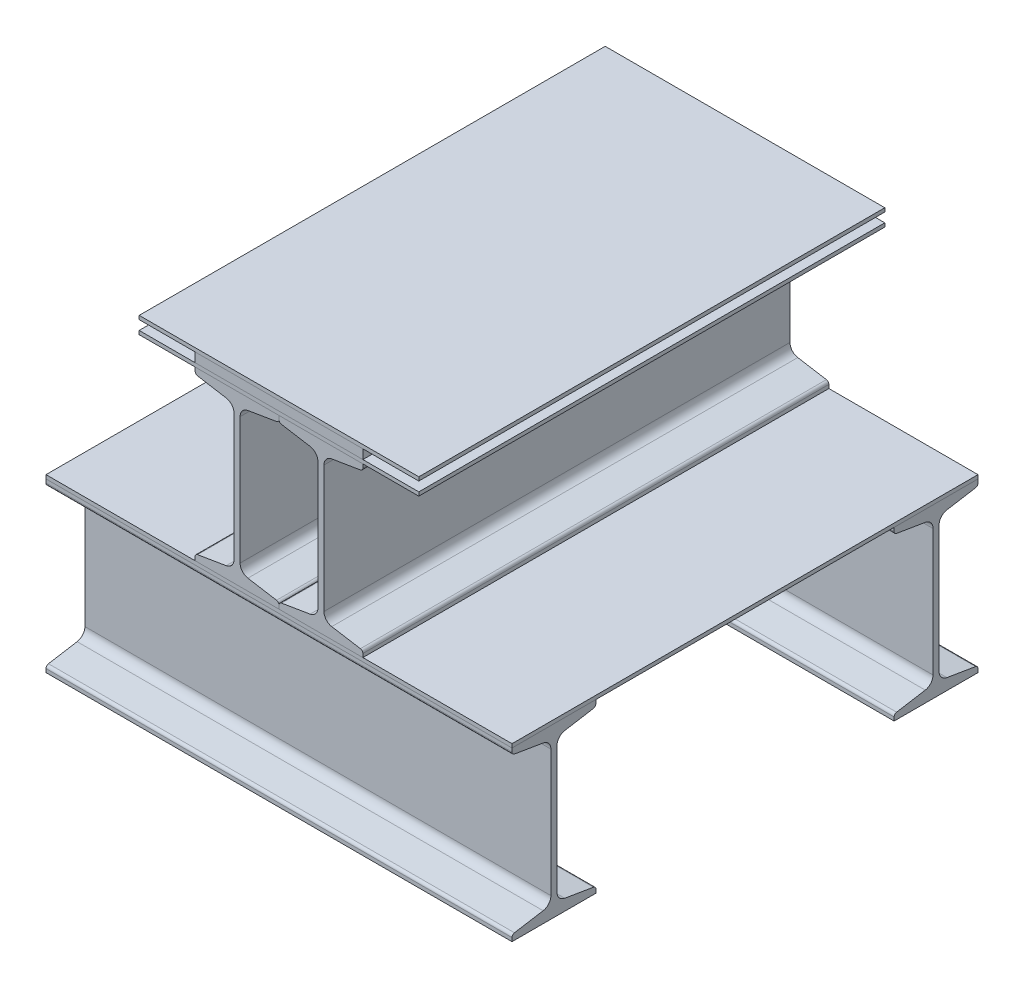
SolidWorks part; units mm, degrees
note: The reader was unsure of these and kept them because the rebuilt part matched: shared geometry of "Sketch132<3>", "Sketch132<4>".
ref_plane "Front Plane" through (0, 0, 0) normal (0, 0, 1) x (1, 0, 0)
ref_plane "Top Plane" through (0, 0, 0) normal (0, 1, 0) x (1, 0, 0)
ref_plane "Right Plane" through (0, 0, 0) normal (1, 0, 0) x (0, 0, -1)
sketch "Sketch1" plane through (0, 0, 0) normal (0, 1, 0) x (1, 0, 0)
  line L0 (250, 0) -> (250, -500) construction
  line L1 (0, 0) -> (500, 0)
  line L2 (0, 0) -> (0, -500)
  line L3 (0, -500) -> (500, -500)
  line L4 (500, 0) -> (500, -500)
  dimension "D1" = 500
  dimension "D2" = 500
ref_plane "Plane9" through (0, 0, 0) normal (1, 0, 0) x (0, 0, -1)
other "Sb beam SB 180 X 23(1)" corner treatment miter
ref_plane "Plane10" through (0, -90, 45) normal (1, 0, 0) x (0, 0, -1)
sketch "Sketch125" plane through (0, -90, 45) normal (1, 0, 0) x (0, 0, -1)
  line L0 (-45, -90) -> (-45, -86.169)
  line L1 (-42.347, -83.0372) -> (-11.6059, -77.9133)
  line L2 (-3.25, -68.0494) -> (-3.25, 68.0494)
  line L3 (-11.6059, 77.9133) -> (-42.347, 83.0372)
  line L4 (-45, 86.169) -> (-45, 90)
  line L5 (-45, 90) -> (45, 90)
  line L6 (45, 90) -> (45, 86.169)
  line L7 (42.347, 83.0372) -> (11.6059, 77.9133)
  line L8 (3.25, 68.0494) -> (3.25, -68.0494)
  line L9 (11.6059, -77.9133) -> (42.347, -83.0372)
  line L10 (45, -86.169) -> (45, -90)
  line L11 (45, -90) -> (-45, -90)
  line L14 (3.3438, -80) -> (-6.9, -80) construction
  line L15 (-3.25, 0) -> (3.25, 0) construction
  arc A0 (-11.6059, -77.9133) -> (-3.25, -68.0494) centre (-13.25, -68.0494) ccw
  arc A1 (-3.25, 68.0494) -> (-11.6059, 77.9133) centre (-13.25, 68.0494) ccw
  arc A2 (11.6059, 77.9133) -> (3.25, 68.0494) centre (13.25, 68.0494) ccw
  arc A3 (3.25, -68.0494) -> (11.6059, -77.9133) centre (13.25, -68.0494) ccw
  arc A4 (45, -86.169) -> (42.347, -83.0372) centre (41.825, -86.169) ccw
  arc A5 (-45, -86.169) -> (-42.347, -83.0372) centre (-41.825, -86.169) cw
  arc A6 (-42.347, 83.0372) -> (-45, 86.169) centre (-41.825, 86.169) cw
  arc A7 (42.347, 83.0372) -> (45, 86.169) centre (41.825, 86.169) ccw
  point P21 (0, 90)
  point P23 (0, -90)
  point P35 (0, 0)
  dimension "D7" = 9.463
  dimension "RI" = 10
  dimension "D2" = 3.175
  dimension "BF" = 90
  dimension "D6" = 9.463
  dimension "DEPTH" = 180
  dimension "TW" = 6.5
  dimension "D1" = 136.0988
  dimension "TF" = 10
other "Sb beam SB 180 X 23(2)" corner treatment miter
ref_plane "Plane11" through (0, -90, 455) normal (1, 0, 0) x (0, 0, -1)
sketch "Sketch127" plane through (0, -90, 455) normal (1, 0, 0) x (0, 0, -1)
  line L0 (-45, -90) -> (-45, -86.169)
  line L1 (-42.347, -83.0372) -> (-11.6059, -77.9133)
  line L2 (-3.25, -68.0494) -> (-3.25, 68.0494)
  line L3 (-11.6059, 77.9133) -> (-42.347, 83.0372)
  line L4 (-45, 86.169) -> (-45, 90)
  line L5 (-45, 90) -> (45, 90)
  line L6 (45, 90) -> (45, 86.169)
  line L7 (42.347, 83.0372) -> (11.6059, 77.9133)
  line L8 (3.25, 68.0494) -> (3.25, -68.0494)
  line L9 (11.6059, -77.9133) -> (42.347, -83.0372)
  line L10 (45, -86.169) -> (45, -90)
  line L11 (45, -90) -> (-45, -90)
  line L14 (3.3438, -80) -> (-6.9, -80) construction
  line L15 (-3.25, 0) -> (3.25, 0) construction
  arc A0 (-11.6059, -77.9133) -> (-3.25, -68.0494) centre (-13.25, -68.0494) ccw
  arc A1 (-3.25, 68.0494) -> (-11.6059, 77.9133) centre (-13.25, 68.0494) ccw
  arc A2 (11.6059, 77.9133) -> (3.25, 68.0494) centre (13.25, 68.0494) ccw
  arc A3 (3.25, -68.0494) -> (11.6059, -77.9133) centre (13.25, -68.0494) ccw
  arc A4 (45, -86.169) -> (42.347, -83.0372) centre (41.825, -86.169) ccw
  arc A5 (-45, -86.169) -> (-42.347, -83.0372) centre (-41.825, -86.169) cw
  arc A6 (-42.347, 83.0372) -> (-45, 86.169) centre (-41.825, 86.169) cw
  arc A7 (42.347, 83.0372) -> (45, 86.169) centre (41.825, 86.169) ccw
  point P21 (0, 90)
  point P23 (0, -90)
  point P35 (0, 0)
  dimension "D7" = 9.463
  dimension "RI" = 10
  dimension "D2" = 3.175
  dimension "BF" = 90
  dimension "D6" = 9.463
  dimension "DEPTH" = 180
  dimension "TW" = 6.5
  dimension "D1" = 136.0988
  dimension "TF" = 10
extrude "Boss-Extrude1" add sketch "Sketch1" along normal blind 4 separate body
ref_plane "Plane14" through (0, 4, 0) normal (0, 1, 0) x (1, 0, 0)
sketch "Sketch119" plane through (0, 4, 0) normal (0, 1, 0) x (1, 0, 0)
  line L0 (250, 0) -> (250, -500)
other "Sb beam SB 180 X 23(3)" corner treatment miter
ref_plane "Plane15" through (295, 94, 0) normal (0, 0, 1) x (1, 0, 0)
sketch "Sketch129" plane through (295, 94, 0) normal (0, 0, 1) x (1, 0, 0)
  line L0 (-45, -90) -> (-45, -86.169)
  line L1 (-42.347, -83.0372) -> (-11.6059, -77.9133)
  line L2 (-3.25, -68.0494) -> (-3.25, 68.0494)
  line L3 (-11.6059, 77.9133) -> (-42.347, 83.0372)
  line L4 (-45, 86.169) -> (-45, 90)
  line L5 (-45, 90) -> (45, 90)
  line L6 (45, 90) -> (45, 86.169)
  line L7 (42.347, 83.0372) -> (11.6059, 77.9133)
  line L8 (3.25, 68.0494) -> (3.25, -68.0494)
  line L9 (11.6059, -77.9133) -> (42.347, -83.0372)
  line L10 (45, -86.169) -> (45, -90)
  line L11 (45, -90) -> (-45, -90)
  line L14 (3.3438, -80) -> (-6.9, -80) construction
  line L15 (-3.25, 0) -> (3.25, 0) construction
  arc A0 (-11.6059, -77.9133) -> (-3.25, -68.0494) centre (-13.25, -68.0494) ccw
  arc A1 (-3.25, 68.0494) -> (-11.6059, 77.9133) centre (-13.25, 68.0494) ccw
  arc A2 (11.6059, 77.9133) -> (3.25, 68.0494) centre (13.25, 68.0494) ccw
  arc A3 (3.25, -68.0494) -> (11.6059, -77.9133) centre (13.25, -68.0494) ccw
  arc A4 (45, -86.169) -> (42.347, -83.0372) centre (41.825, -86.169) ccw
  arc A5 (-45, -86.169) -> (-42.347, -83.0372) centre (-41.825, -86.169) cw
  arc A6 (-42.347, 83.0372) -> (-45, 86.169) centre (-41.825, 86.169) cw
  arc A7 (42.347, 83.0372) -> (45, 86.169) centre (41.825, 86.169) ccw
  point P21 (0, 90)
  point P23 (0, -90)
  point P35 (0, 0)
  dimension "D7" = 9.463
  dimension "RI" = 10
  dimension "D2" = 3.175
  dimension "BF" = 90
  dimension "D6" = 9.463
  dimension "DEPTH" = 180
  dimension "TW" = 6.5
  dimension "D1" = 136.0988
  dimension "TF" = 10
other "Sb beam SB 180 X 23(4)" corner treatment miter
ref_plane "Plane16" through (205, 94, 0) normal (0, 0, 1) x (1, 0, 0)
sketch "Sketch131" plane through (205, 94, 0) normal (0, 0, 1) x (1, 0, 0)
  line L0 (-45, -90) -> (-45, -86.169)
  line L1 (-42.347, -83.0372) -> (-11.6059, -77.9133)
  line L2 (-3.25, -68.0494) -> (-3.25, 68.0494)
  line L3 (-11.6059, 77.9133) -> (-42.347, 83.0372)
  line L4 (-45, 86.169) -> (-45, 90)
  line L5 (-45, 90) -> (45, 90)
  line L6 (45, 90) -> (45, 86.169)
  line L7 (42.347, 83.0372) -> (11.6059, 77.9133)
  line L8 (3.25, 68.0494) -> (3.25, -68.0494)
  line L9 (11.6059, -77.9133) -> (42.347, -83.0372)
  line L10 (45, -86.169) -> (45, -90)
  line L11 (45, -90) -> (-45, -90)
  line L14 (3.3438, -80) -> (-6.9, -80) construction
  line L15 (-3.25, 0) -> (3.25, 0) construction
  arc A0 (-11.6059, -77.9133) -> (-3.25, -68.0494) centre (-13.25, -68.0494) ccw
  arc A1 (-3.25, 68.0494) -> (-11.6059, 77.9133) centre (-13.25, 68.0494) ccw
  arc A2 (11.6059, 77.9133) -> (3.25, 68.0494) centre (13.25, 68.0494) ccw
  arc A3 (3.25, -68.0494) -> (11.6059, -77.9133) centre (13.25, -68.0494) ccw
  arc A4 (45, -86.169) -> (42.347, -83.0372) centre (41.825, -86.169) ccw
  arc A5 (-45, -86.169) -> (-42.347, -83.0372) centre (-41.825, -86.169) cw
  arc A6 (-42.347, 83.0372) -> (-45, 86.169) centre (-41.825, 86.169) cw
  arc A7 (42.347, 83.0372) -> (45, 86.169) centre (41.825, 86.169) ccw
  point P21 (0, 90)
  point P23 (0, -90)
  point P35 (0, 0)
  dimension "D7" = 9.463
  dimension "RI" = 10
  dimension "D2" = 3.175
  dimension "BF" = 90
  dimension "D6" = 9.463
  dimension "DEPTH" = 180
  dimension "TW" = 6.5
  dimension "D1" = 136.0988
  dimension "TF" = 10
sketch "Sketch132" plane through (0, 4, 0) normal (0, 1, 0) x (1, 0, 0)
  line L0 (0, 0) -> (500, 0) construction
  line L1 (100, 0) -> (400, 0)
  line L2 (100, 0) -> (100, -500)
  line L3 (100, -500) -> (400, -500)
  line L4 (400, 0) -> (400, -500)
  line L5 (0, -500) -> (500, -500) construction
  line L6 (250, 0) -> (250, -500) construction
  line L8 (160, 0) -> (340, 0)
  line L9 (160, 0) -> (160, -500)
  line L10 (160, -500) -> (340, -500)
  line L11 (340, 0) -> (340, -500)
  dimension "D1" = 300
  dimension "D2" = 150
extrude "Boss-Extrude2" add sketch "Sketch132" along normal blind 4 from surface at 180 separate body contours L9 L1 L2 L3 | L1 L11 L3 L4 | L11 L1 L9 L3 starting at face at (205, 184, 250)
extrude "Boss-Extrude3" add sketch "Sketch132<3>" along normal blind 10 from surface at 184 separate body contours L11 L1 L9 L3 starting at face at (250, 188, 250)
sketch "Sketch132<3>" plane through (0, 4, 0) normal (0, 1, 0) x (1, 0, 0) same geometry as "Sketch132"
extrude "Boss-Extrude4" add sketch "Sketch132<4>" along normal blind 4 from surface at 194 separate body contours L11 L1 L9 L3 | L1 L11 L3 L4 | L9 L1 L2 L3 starting at face at (250, 198, 250)
sketch "Sketch132<4>" plane through (0, 4, 0) normal (0, 1, 0) x (1, 0, 0) same geometry as "Sketch132"
